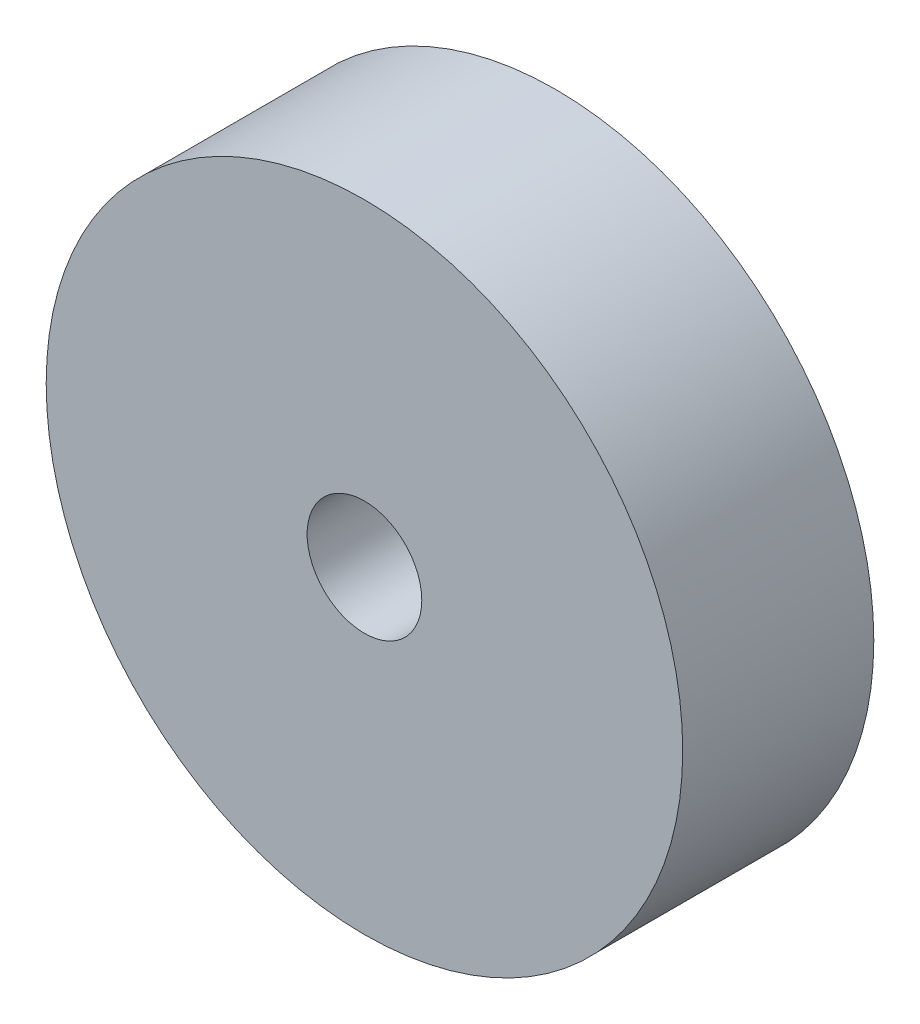
SolidWorks part; units mm, degrees
ref_plane "Plano frontal" through (0, 0, 0) normal (0, 0, 1) x (1, 0, 0)
ref_plane "Plano superior" through (0, 0, 0) normal (0, 1, 0) x (1, 0, 0)
ref_plane "Plano direito" through (0, 0, 0) normal (1, 0, 0) x (0, 0, -1)
sketch "Esboço1" plane through (0, 0, -10) normal (0, 0, 1) x (1, 0, 0)
  circle A0 centre (175.26, 0) radius 7.14
  circle A1 centre (175.26, 0) radius 16.6556
  circle A3 centre (175.26, 0) radius 7.14 construction
  circle A4 centre (175.26, 0) radius 14.6556 construction
  circle A5 centre (153.7069, -5.1317) radius 7.5 construction
  circle A6 centre (175.26, 0) radius 7.14 construction
  dimension "D1" = 2
extrude "Ressalto-extrusão1" add sketch "Esboço1" against normal up to surface (5 mm away) contours A0
extrude "Ressalto-extrusão2" add sketch "Esboço1<3>" along normal up to surface (10 mm away) contours A1
sketch "Esboço1<3>" plane through (0, 0, -10) normal (0, 0, 1) x (1, 0, 0) same geometry as "Esboço1"
sketch "Esboço2" plane through (0, 0, 0) normal (0, 0, 1) x (1, 0, 0)
  circle A0 centre (175.26, 0) radius 3
  dimension "D1" = 6
extrude "Corte-extrusão1" cut sketch "Esboço2" against normal through all
